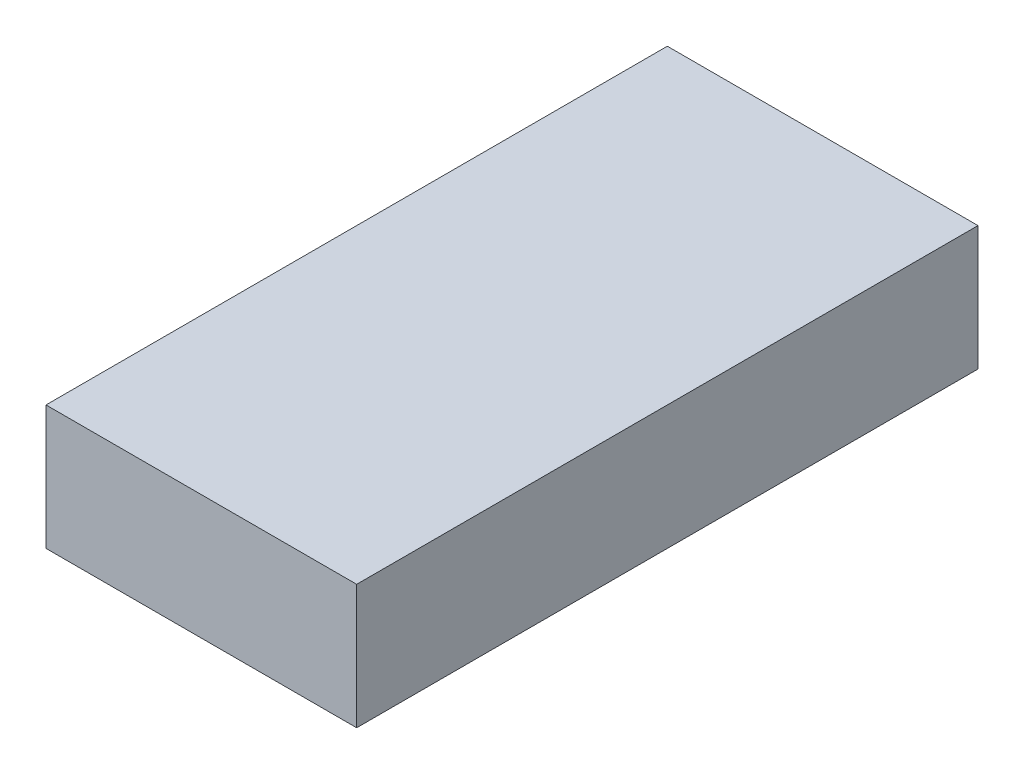
SolidWorks part; units mm, degrees
ref_plane "Спереди" through (0, 0, 0) normal (0, 0, 1) x (1, 0, 0)
ref_plane "Сверху" through (0, 0, 0) normal (0, 1, 0) x (1, 0, 0)
ref_plane "Справа" through (0, 0, 0) normal (1, 0, 0) x (0, 0, -1)
sketch "Эскиз1" plane through (0, 0, 0) normal (1, 0, 0) x (0, 0, -1)
  line L1 (0, 0) -> (20, 0)
  line L2 (0, 0) -> (0, 4)
  line L3 (0, 4) -> (20, 4)
  line L4 (20, 0) -> (20, 4)
extrude "Бобышка-Вытянуть1" add sketch "Эскиз1" along normal blind 10
